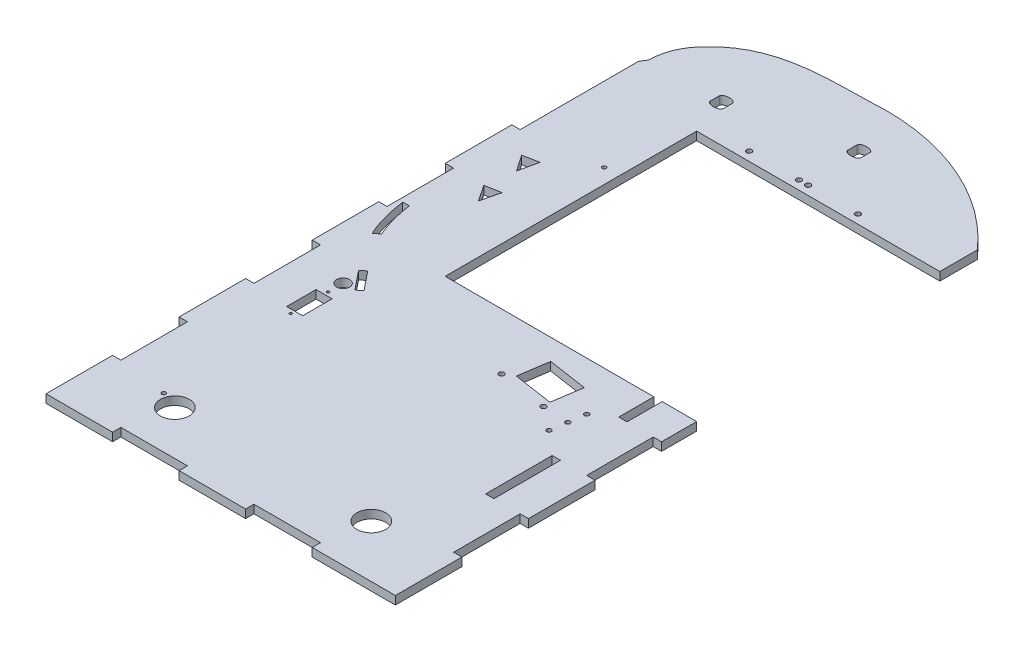
SolidWorks part; units mm, degrees
ref_plane "Front Plane" through (0, 0, 0) normal (0, 0, 1) x (1, 0, 0)
ref_plane "Top Plane" through (0, 0, 0) normal (0, 1, 0) x (1, 0, 0)
ref_plane "Right Plane" through (0, 0, 0) normal (1, 0, 0) x (0, 0, -1)
sketch "Sketch2" plane through (0, 0, 0) normal (0, 1, 0) x (1, 0, 0)
  line L0 (127, 0) -> (127, 40) construction
  line L1 (0, 0) -> (254, 0)
  line L2 (0, 0) -> (0, 508)
  line L3 (0, 508) -> (254, 508)
  line L4 (254, 0) -> (254, 508)
  line L5 (112, 0) -> (112, 40) construction
  line L6 (70.0293, 132.7246) -> (75.0014, 133.2514) construction
  line L8 (3.0464, 262.9295) -> (8.0974, 262.9295)
  line L9 (12.0177, 230.6311) -> (16.1196, 233.6878)
  line L10 (63.9635, 154.4733) -> (68.5195, 156.533) construction
  line L11 (31.3299, 200.9155) -> (35.2571, 204.0102)
  line L12 (42.9806, 186.4099) -> (46.8891, 189.5281)
  line L13 (27.8154, 172.0099) -> (40.0654, 172.0099)
  line L14 (27.8154, 172.0099) -> (27.8154, 149.5599)
  line L15 (40.0654, 172.0099) -> (40.0654, 149.5599)
  line L16 (27.8154, 149.5599) -> (40.0654, 149.5599)
  line L17 (0, 367.5) -> (57.0274, 367.5) construction
  line L20 (0, 358) -> (56.5933, 358) construction
  line L21 (57.0274, 367.5) -> (57.0274, 358) construction
  line L22 (138.65, 474.05) -> (138.65, 467.05) construction
  line L23 (148.65, 467.05) -> (148.65, 474.05) construction
  line L24 (138.65, 474.05) -> (138.65, 467.05)
  line L25 (148.65, 467.05) -> (148.65, 474.05)
  line L26 (63.65, 447.05) -> (63.65, 454.05) construction
  line L27 (53.65, 454.05) -> (53.65, 447.05) construction
  line L28 (63.65, 447.05) -> (63.65, 454.05)
  line L29 (53.65, 454.05) -> (53.65, 447.05)
  line L32 (195.0465, 209.5031) -> (191.6211, 186.7241)
  line L33 (191.6211, 186.7241) -> (161.4863, 191.2557)
  line L34 (161.4863, 191.2557) -> (164.9117, 214.0346)
  line L35 (164.9117, 214.0346) -> (195.0465, 209.5031)
  line L38 (29.2137, 341.5913) -> (17.4353, 339.2955)
  line L40 (17.4353, 339.2955) -> (25.9547, 326.9496)
  line L47 (25.9547, 326.9496) -> (29.2137, 341.5913)
  line L48 (34.7792, 307.0354) -> (22.9615, 304.9516)
  line L49 (22.9615, 304.9516) -> (31.2577, 292.4546)
  line L50 (31.2577, 292.4546) -> (34.7792, 307.0354)
  line L51 (0, 311.1437) -> (42.9806, 311.1437) construction
  circle A0 centre (52, 40) radius 11
  circle A1 centre (202, 40) radius 11
  circle A2 centre (38.2469, 45.3329) radius 1.5
  circle A3 centre (34.0154, 186.4099) radius 5
  arc A4 (33.4154, 175.7599) -> (34.6154, 175.7599) centre (34.0154, 174.9599) ccw construction
  arc A5 (33.4154, 175.7599) -> (34.6154, 175.7599) centre (34.0154, 174.9599) ccw
  arc A6 (34.6154, 175.7599) -> (33.4154, 175.7599) centre (34.0154, 174.9599) ccw
  arc A7 (34.6154, 145.6599) -> (33.4154, 145.6599) centre (34.0154, 146.4599) ccw construction
  arc A8 (34.6154, 145.6599) -> (33.4154, 145.6599) centre (34.0154, 146.4599) ccw
  arc A9 (34.6154, 145.6599) -> (33.4154, 145.6599) centre (34.0154, 146.4599) cw
  circle A10 centre (57.0274, 362.75) radius 1.5
  circle A11 centre (184.6289, 428.7954) radius 2 construction
  circle A12 centre (146.6289, 428.7954) radius 2 construction
  circle A13 centre (139.6289, 428.7954) radius 2 construction
  circle A14 centre (101.6289, 428.7954) radius 2 construction
  circle A15 centre (184.6289, 428.7954) radius 2
  circle A16 centre (146.6289, 428.7954) radius 2
  circle A17 centre (139.6289, 428.7954) radius 2
  circle A18 centre (101.6289, 428.7954) radius 2
  circle A19 centre (154.4066, 187.01) radius 2 construction
  circle A20 centre (191.9904, 181.4011) radius 2 construction
  circle A21 centre (213.5907, 192.7999) radius 1.75 construction
  circle A22 centre (211.7247, 180.2964) radius 1.75 construction
  circle A23 centre (209.8587, 167.7928) radius 1.75 construction
  circle A24 centre (154.4066, 187.01) radius 2
  circle A25 centre (191.9904, 181.4011) radius 2
  circle A26 centre (213.5907, 192.7999) radius 1.75
  circle A27 centre (211.7247, 180.2964) radius 1.75
  circle A28 centre (209.8587, 167.7928) radius 1.75
  ellipse E0 centre (143.65, 474.05) end of major axis (138.65, 474.05) minor radius 2.5 (148.65, 474.05) -> (138.65, 474.05) ccw construction
  ellipse E1 centre (143.65, 467.05) end of major axis (138.65, 467.05) minor radius 2.5 (138.65, 467.05) -> (148.65, 467.05) ccw construction
  ellipse E2 centre (143.65, 467.05) end of major axis (138.65, 467.05) minor radius 2.5 (138.65, 467.05) -> (148.65, 467.05) ccw
  ellipse E3 centre (143.65, 474.05) end of major axis (138.65, 474.05) minor radius 2.5 (148.65, 474.05) -> (138.65, 474.05) ccw
  ellipse E4 centre (58.65, 447.05) end of major axis (63.65, 447.05) minor radius 2.5 (53.65, 447.05) -> (63.65, 447.05) ccw construction
  ellipse E5 centre (58.65, 454.05) end of major axis (63.65, 454.05) minor radius 2.5 (63.65, 454.05) -> (53.65, 454.05) ccw construction
  ellipse E6 centre (58.65, 447.05) end of major axis (63.65, 447.05) minor radius 2.5 (53.65, 447.05) -> (63.65, 447.05) ccw
  ellipse E7 centre (58.65, 454.05) end of major axis (63.65, 454.05) minor radius 2.5 (63.65, 454.05) -> (53.65, 454.05) ccw
  spline S0 degree 3 poles (0, 358) (10.2414, 318.2744) (-10.3205, 225.9555) (70.6512, 174.3118) (75.0014, 133.2514) knots 0 0 0 0 0.517006 1 1 1 1 construction
  spline S1 degree 3 poles (57.0275, 368.1055) (57.1037, 341.1276) (39.9806, 298.3045) (60.6873, 235.4301) (84.735, 206.7039) (104.9746, 198.8412) knots 0 0 0 0 0.425424 0.675791 1 1 1 1 construction
  spline S2 degree 1 poles (-4.8417, 356.7518) (70.0293, 132.7246) knots 0 0 1 1 construction
  spline S3 degree 3 poles (-4.8417, 356.7518) (-4.2453, 354.4384) (-3.2098, 349.8001) (-1.6146, 340.1963) (-0.4104, 327.7832) (0.2492, 312.4005) (0.7261, 291.8409) (1.4026, 275.812) (2.8811, 264.0829) (3.206, 261.7747) (3.5674, 259.4757) (3.9542, 257.1833) (4.5302, 254.1018) (5.5014, 249.6086) (6.6895, 245.0428) (8.2086, 240.135) (9.6429, 236.1559) (11.2633, 232.2426) (12.5555, 229.4544) (14.3601, 225.8497) (18.1885, 218.946) (23.3984, 211.2859) (29.2816, 203.4962) (32.93, 198.8824) (36.8298, 194.0373) (40.7355, 189.2215) (46.6866, 181.7864) (53.9965, 172.1125) (59.9683, 162.643) (63.1245, 156.3309) (64.1438, 154.0765) (64.4933, 153.279) (64.8362, 152.4792) (65.7137, 150.3629) (66.7102, 147.6655) (67.6191, 144.7625) (68.2641, 142.4625) (68.8611, 140.0122) (69.3531, 137.5307) (69.7433, 135.1238) (69.9343, 133.621) (70.0293, 132.7246) knots 0 0 0 0 0.03125 0.0625 0.125 0.1875 0.25 0.371368 0.378402 0.392471 0.399505 0.406539 0.420608 0.4375 0.462351 0.477976 0.5 0.513677 0.529302 0.537114 0.5625 0.625 0.649179 0.680429 0.696054 0.724459 0.755709 0.8125 0.875 0.898852 0.904562 0.907417 0.910272 0.915981 0.9375 0.948072 0.955885 0.96875 0.980913 0.988548 1 1 1 1 only from (0, 317.7537) to (70.0293, 132.7246) construction
  spline S4 degree 1 poles (35.2571, 204.0102) (46.8891, 189.5281) knots 0 0 1 1
  spline S5 degree 1 poles (31.3299, 200.9155) (42.9806, 186.4099) knots 0 0 1 1
  spline S6 degree 3 poles (3.0464, 262.9295) (4.6075, 251.8412) (7.2857, 240.8284) (12.0177, 230.6311) knots 0 0 0 0 1 1 1 1
  spline S7 degree 3 poles (8.0974, 262.9295) (9.5523, 252.911) (11.965, 242.952) (16.1196, 233.6878) knots 0 0 0 0 1 1 1 1
  spline S8 degree 3 poles (68.5195, 156.533) (70.3934, 152.3928) (73.1628, 144.7538) (74.6292, 136.7727) (75.0014, 133.2514) knots 0 0 0 0 0.562151 1 1 1 1 construction
  spline S9 degree 3 poles (63.9635, 154.4733) (65.5406, 150.9864) (68.1883, 143.8779) (69.6381, 136.4314) (70.0293, 132.7246) knots 0 0 0 0 0.506681 1 1 1 1 construction
  dimension "D3" = 22
  dimension "D9" = 3
  dimension "D10" = 3
  dimension "D1" = 508
  dimension "D2" = 254
  dimension "D4" = 40
  dimension "D5" = 15
  dimension "D6" = 60
  dimension "D7" = 150
  dimension "D11" = 10
  dimension "D12" = 15
  dimension "D13" = 12
  dimension "D14" = 12
  dimension "D15" = 15
  dimension "D8" = 5
extrude "Boss-Extrude1" add sketch "Sketch2" along normal blind 6.35
sketch "Sketch3" plane through (0, 6.35, 0) normal (0, 1, 0) x (1, 0, 0)
  line L0 (127, 508) -> (127, 338.6667) construction
  line L1 (254, 508) -> (0, 508) construction
  line L2 (127, 338.6667) -> (127, 169.3333) construction
  line L3 (127, 169.3333) -> (127, 0) construction
  line L4 (0, 0) -> (254, 0) construction
  line L5 (254, 0) -> (254, 508) construction
  line L6 (254, 508) -> (127, 508)
  line L7 (254, 450.6701) -> (254, 508)
  arc A1 (127, 508) -> (254, 450.6701) centre (127, 338.6667) cw
extrude "Cut-Extrude1" cut sketch "Sketch3" against normal up to next
sketch "Sketch5" plane through (0, 6.35, 0) normal (0, 1, 0) x (1, 0, 0)
  line L0 (254, 450.6701) -> (0, 450.6701) construction
  line L1 (0, 508) -> (0, 0) construction
  line L2 (3, 450.6701) -> (0, 445.8071)
  line L3 (0, 508) -> (0, 445.8071)
  line L6 (0, 508) -> (0, 526.7662)
  line L7 (0, 526.7662) -> (127, 526.7662)
  line L8 (127, 508) -> (127, 526.7662)
  circle A0 centre (45, 450.6701) radius 22 construction
  arc A2 (16.9934, 481.9692) -> (3, 450.6701) centre (45, 450.6701) ccw
  circle A3 centre (45, 450.6701) radius 42 construction
  spline S0 degree 3 poles (16.9934, 481.9692) (44.7711, 511.7661) (91.2093, 505.8566) (127, 508) knots 0 0 0 0 1 1 1 1
  dimension "D1" = 44
  dimension "D3" = 45
  dimension "D2" = 20
extrude "Cut-Extrude2" cut sketch "Sketch5" against normal up to next
sketch "Sketch7" plane through (0, 0, 0) normal (0, -1, 0) x (1, 0, 0)
  line L1 (254, 0) -> (260.35, 0)
  line L2 (254, 0) -> (254, -50.8)
  line L3 (254, -50.8) -> (260.35, -50.8)
  line L4 (260.35, 0) -> (260.35, -50.8)
  line L5 (0, 0) -> (-6.35, 0)
  line L6 (0, 0) -> (0, -50.8)
  line L7 (0, -50.8) -> (-6.35, -50.8)
  line L8 (-6.35, 0) -> (-6.35, -50.8)
  dimension "D1" = 6.35
  dimension "D2" = 50.8
  dimension "D3" = 6.35
  dimension "D4" = 50.8
extrude "Boss-Extrude2" add sketch "Sketch7" against normal up to surface (6.35 mm away) up to face at (24.2012, 6.35, -335.9455)
pattern_linear "LPattern1" count 4 spacing 101.6 along (0, 0, -1) of "Boss-Extrude2"
sketch "Sketch8" plane through (0, 6.35, 0) normal (0, 1, 0) x (1, 0, 0)
  line L0 (254, 152.4) -> (254, 203.2) construction
  line L5 (234, 152.4) -> (227.65, 152.4)
  line L7 (234, 152.4) -> (234, 101.6)
  line L9 (234, 101.6) -> (227.65, 101.6)
  line L10 (227.65, 152.4) -> (227.65, 101.6)
  line L11 (254, 101.6) -> (260.35, 101.6) construction
  line L12 (260.35, 101.6) -> (260.35, 152.4) construction
  dimension "D1" = 20
extrude "Cut-Extrude3" cut sketch "Sketch8" against normal up to next
pattern_linear "LPattern2" count 3 spacing 101.6 along (0, 0, -1) of "Cut-Extrude3"
sketch "Slider" plane through (0, 6.35, 6.35) normal (0, 1, 0) x (1, 0, 0)
  line L0 (0, 452.1571) -> (0, 361.95) construction
  line L6 (54.1176, 177.8402) -> (58.2442, 180.6634) construction
  spline S0 degree 3 poles (0, 364.2407) (10.0932, 324.5031) (-6.7408, 249.3382) (44.5453, 200.6868) (58.2442, 180.6634) knots 0 0 0 0 0.63201 1 1 1 1 construction
  spline S1 degree 3 poles (57.0275, 368.1055) (60.011, 340.8516) (38.8621, 298.2828) (61.0822, 235.4033) (84.5865, 206.7018) (104.9746, 198.8412) knots 0 0 0 0 0.426438 0.676001 1 1 1 1 construction
  spline S2 degree 1 poles (-4.8461, 363.0098) (54.1176, 177.8402) knots 0 0 1 1 construction
  spline S3 degree 3 poles (-4.8461, 363.0098) (-4.3659, 361.1191) (-3.5097, 357.3301) (-2.1229, 349.5349) (-0.9477, 339.5089) (-0.1716, 327.1083) (0.3662, 310.2426) (0.7835, 288.8153) (2.7416, 267.6076) (6.4419, 251.188) (10.6067, 239.2328) (16.4686, 227.9252) (23.4848, 217.3517) (31.2063, 207.235) (39.1962, 197.3973) (45.7189, 189.2885) (50.658, 182.7615) (52.9812, 179.5011) (54.1176, 177.8402) knots 0 0 0 0 0.03125 0.0625 0.125 0.1875 0.25 0.375 0.5 0.5625 0.625 0.6875 0.75 0.8125 0.875 0.9375 0.96875 1 1 1 1 only from (0, 321.3493) to (54.1176, 177.8402) construction
  dimension "D8" = 5
sketch "Sketch9" plane through (0, 6.35, 0) normal (0, 1, 0) x (1, 0, 0)
  line L0 (260.35, 0) -> (260.35, 50.8) construction
  line L1 (68.35, 422) -> (260.35, 422)
  line L2 (68.35, 422) -> (68.35, 230)
  line L3 (68.35, 230) -> (260.35, 230)
  line L4 (260.35, 422) -> (260.35, 230)
  line L5 (68.35, 422) -> (260.35, 230) construction
  line L6 (68.35, 230) -> (260.35, 422) construction
  line L8 (-6.35, 0) -> (260.35, 0) construction
  point P4 (164.35, 326)
  dimension "D1" = 192
  dimension "D2" = 192
  dimension "D3" = 230
extrude "Cut-Extrude4" cut sketch "Sketch9" against normal up to surface (6.35 mm away) up to face at (230.825, 0, -228.6)
sketch "Sketch10" plane through (0, 6.35, 0) normal (0, 1, 0) x (1, 0, 0)
  line L0 (-6.35, 0) -> (260.35, 0) construction
  line L1 (-6.35, 50.8) -> (-6.35, 0) construction
  line L2 (44.45, 6.35) -> (95.25, 6.35)
  line L3 (44.45, 6.35) -> (44.45, 0)
  line L4 (44.45, 0) -> (95.25, 0)
  line L5 (95.25, 6.35) -> (95.25, 0)
  line L6 (44.45, 6.35) -> (95.25, 0) construction
  line L7 (44.45, 0) -> (95.25, 6.35) construction
  point P4 (69.85, 3.175)
  point P7 (39.5572, 4.2978)
  dimension "D1" = 50.8
  dimension "D2" = 50.8
  dimension "D3" = 6.35
extrude "Cut-Extrude5" cut sketch "Sketch10" against normal up to next
pattern_linear "LPattern3" count 2 spacing 101.6 along (1, 0, 0) of "Cut-Extrude5"
